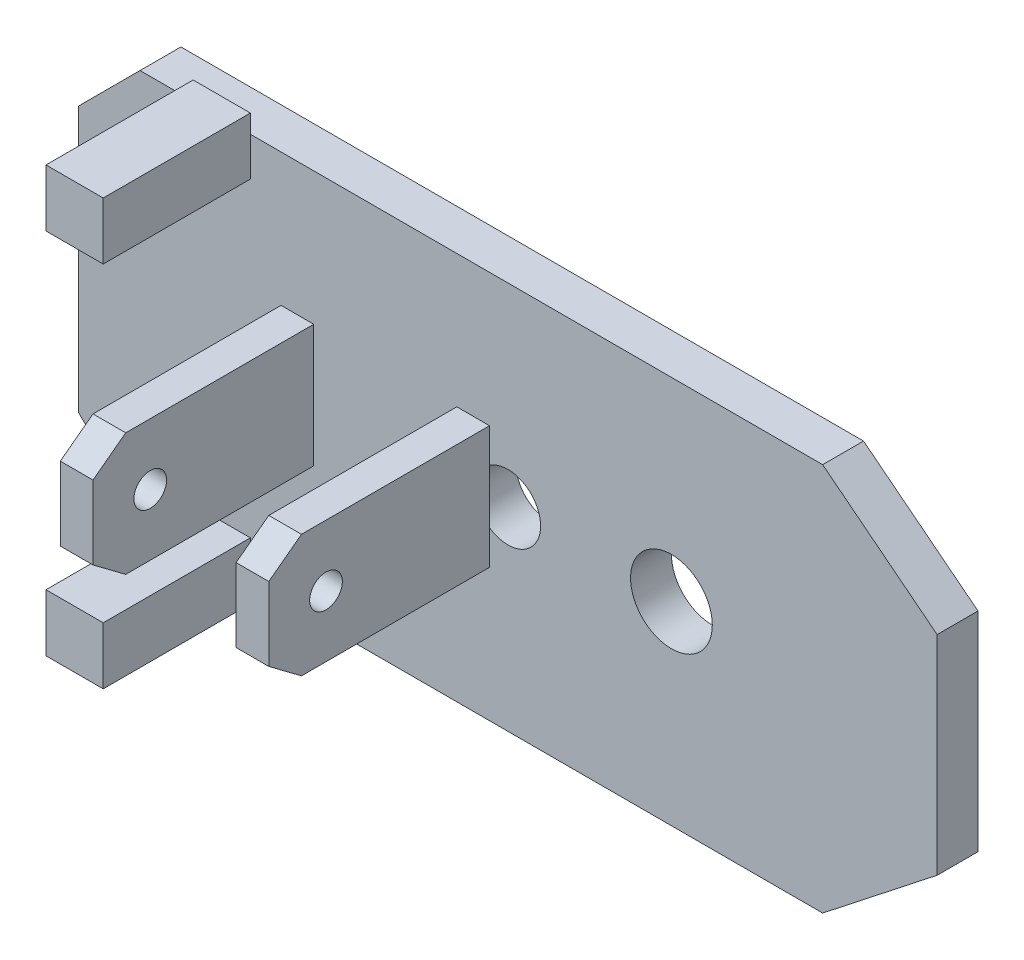
SolidWorks part; units mm, degrees
ref_plane "Front Plane" through (0, 0, 0) normal (0, 0, 1) x (1, 0, 0)
ref_plane "Top Plane" through (0, 0, 0) normal (0, 1, 0) x (1, 0, 0)
ref_plane "Right Plane" through (0, 0, 0) normal (1, 0, 0) x (0, 0, -1)
ref_plane "PL_Sole_Plate_base" through (0, 0, -50) normal (0, 0, 1) x (1, 0, 0)
sketch "SK_Sole_Plate" plane through (0, 0, -50) normal (0, 0, 1) x (1, 0, 0)
  line L0 (-60, -47.5) -> (107, -47.5)
  line L1 (107, -47.5) -> (135, -25.5)
  line L2 (135, -25.5) -> (135, 25.5)
  line L3 (135, 25.5) -> (107, 47.5)
  line L4 (107, 47.5) -> (-60, 47.5)
  line L5 (-60, 47.5) -> (-75, 32.5)
  line L6 (-75, 32.5) -> (-75, -32.5)
  line L7 (-75, -32.5) -> (-60, -47.5)
  circle A0 centre (70, 0) radius 10
  circle A1 centre (30, 0) radius 8
  dimension "D17_SK_Sole_Plate" = 20
  dimension "D19_SK_Sole_Plate" = 16
  dimension "P1" = 60
  dimension "P2" = 47.5
  dimension "P3" = 107
  dimension "P4" = 47.5
  dimension "P5" = 135
  dimension "P6" = 25.5
  dimension "P7" = 135
  dimension "P8" = 25.5
  dimension "P9" = 107
  dimension "P10" = 47.5
  dimension "P11" = 60
  dimension "P12" = 47.5
  dimension "P13" = 75
  dimension "P14" = 32.5
  dimension "P15" = 75
  dimension "P16" = 32.5
  dimension "P18" = 70
  dimension "P20" = 30
extrude "Sole_Plate" add sketch "SK_Sole_Plate" along normal blind 10
ref_plane "PL_Clevis_Front_base" through (17.5, 0, 0) normal (1, 0, 0) x (0, 0, -1)
sketch "SK_Clevis_Front" plane through (17.5, 0, 0) normal (1, 0, 0) x (0, 0, -1)
  line L0 (40, -15) -> (40, 15)
  line L1 (40, 15) -> (-6, 15)
  line L2 (-6, 15) -> (-14, 9)
  line L3 (-14, 9) -> (-14, -9)
  line L4 (-14, -9) -> (-6, -15)
  line L5 (-6, -15) -> (40, -15)
  circle A0 centre (0, 0) radius 4
  dimension "D13_SK_Clevis_Front" = 8
  dimension "P1" = 40
  dimension "P2" = 15
  dimension "P3" = 40
  dimension "P4" = 15
  dimension "P5" = 6
  dimension "P6" = 15
  dimension "P7" = 14
  dimension "P8" = 9
  dimension "P9" = 14
  dimension "P10" = 9
  dimension "P11" = 6
  dimension "P12" = 15
extrude "Clevis_Front" add sketch "SK_Clevis_Front" along normal blind 8
ref_plane "PL_Clevis_Back_base" through (-25.5, 0, 0) normal (1, 0, 0) x (0, 0, -1)
sketch "SK_Clevis_Back" plane through (-25.5, 0, 0) normal (1, 0, 0) x (0, 0, -1)
  line L0 (40, -15) -> (40, 15)
  line L1 (40, 15) -> (-6, 15)
  line L2 (-6, 15) -> (-14, 9)
  line L3 (-14, 9) -> (-14, -9)
  line L4 (-14, -9) -> (-6, -15)
  line L5 (-6, -15) -> (40, -15)
  circle A0 centre (0, 0) radius 4
  dimension "D13_SK_Clevis_Back" = 8
  dimension "P1" = 40
  dimension "P2" = 15
  dimension "P3" = 40
  dimension "P4" = 15
  dimension "P5" = 6
  dimension "P6" = 15
  dimension "P7" = 14
  dimension "P8" = 9
  dimension "P9" = 14
  dimension "P10" = 9
  dimension "P11" = 6
  dimension "P12" = 15
extrude "Clevis_Back" add sketch "SK_Clevis_Back" along normal blind 8
ref_plane "PL_Post_Lat_base" through (0, 0, -40) normal (0, 0, 1) x (1, 0, 0)
sketch "SK_Post_Lat" plane through (0, 0, -40) normal (0, 0, 1) x (1, 0, 0)
  line L0 (-47, 38) -> (-33, 38)
  line L1 (-33, 38) -> (-33, 52)
  line L2 (-33, 52) -> (-47, 52)
  line L3 (-47, 52) -> (-47, 38)
  dimension "P1" = 47
  dimension "P2" = 38
  dimension "P3" = 33
  dimension "P4" = 38
  dimension "P5" = 33
  dimension "P6" = 52
  dimension "P7" = 47
  dimension "P8" = 52
extrude "Post_Lat" add sketch "SK_Post_Lat" along normal blind 36
ref_plane "PL_Post_Med_base" through (0, 0, -40) normal (0, 0, 1) x (1, 0, 0)
sketch "SK_Post_Med" plane through (0, 0, -40) normal (0, 0, 1) x (1, 0, 0)
  line L0 (-47, -52) -> (-33, -52)
  line L1 (-33, -52) -> (-33, -38)
  line L2 (-33, -38) -> (-47, -38)
  line L3 (-47, -38) -> (-47, -52)
  dimension "P1" = 47
  dimension "P2" = 52
  dimension "P3" = 33
  dimension "P4" = 52
  dimension "P5" = 33
  dimension "P6" = 38
  dimension "P7" = 47
  dimension "P8" = 38
extrude "Post_Med" add sketch "SK_Post_Med" along normal blind 36
equation "\"Foot_length\" = 210"
equation "\"Foot_width\" = 95"
equation "\"Ankle_height\" = 50"
